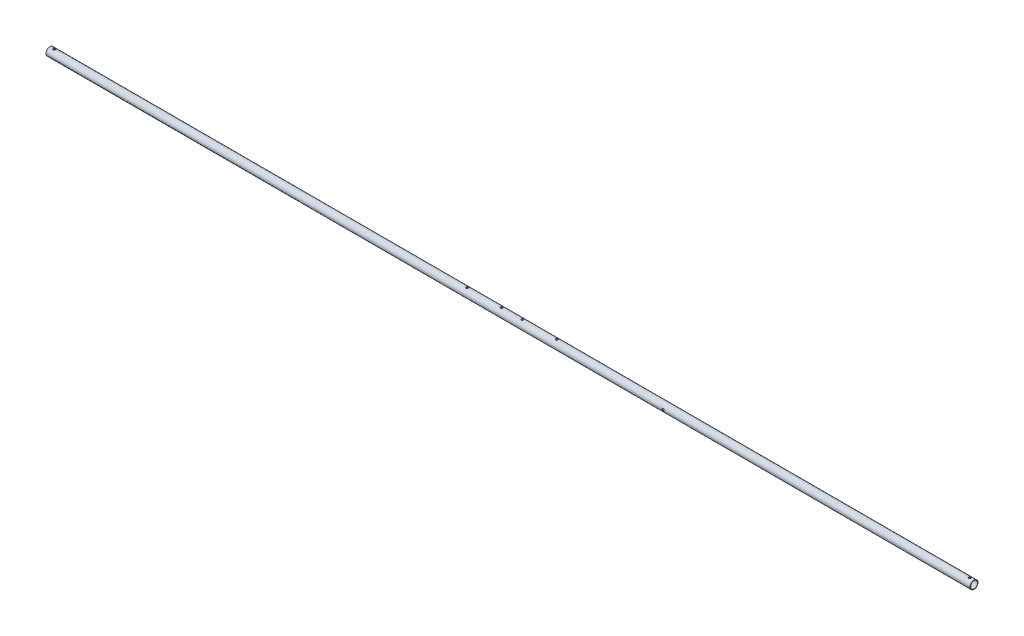
SolidWorks part; units mm, degrees
other "DetailItem1"
material "Galvanized Steel"
ref_plane "Front Plane" through (0, 0, 0) normal (0, 0, 1) x (1, 0, 0)
ref_plane "Top Plane" through (0, 0, 0) normal (0, 1, 0) x (1, 0, 0)
ref_plane "Right Plane" through (0, 0, 0) normal (1, 0, 0) x (0, 0, -1)
sketch "Sketch3" plane through (0, 0, 0) normal (1, 0, 0) x (0, 0, -1)
  circle A0 centre (0, 0) radius 10.4648
  circle A1 centre (0, 0) radius 11.7094
  dimension "D1" = 20.9296
  dimension "D2" = 23.4188
extrude "Boss-Extrude1" add sketch "Sketch3" along normal blind 2724.912
sketch "Sketch4" plane through (0, 0, 0) normal (0, 1, 0) x (1, 0, 0)
  line L0 (0, 11.7094) -> (0, -11.7094) construction
  circle A0 centre (1331.976, 0) radius 3.175
  circle A1 centre (1392.936, 0) radius 3.175
  circle A2 centre (1494.6376, 0) radius 3.175
  circle A3 centre (1230.2744, 0) radius 3.175
  point P0 (1362.456, 0)
  point P1 (1392.936, 0)
  point P3 (1331.976, 0)
  dimension "D4" = 6.35
  dimension "D5" = 6.35
  dimension "D6" = 132.1816
  dimension "D1" = 1362.456
  dimension "D2" = 30.48
  dimension "D3" = 30.48
  dimension "D7" = 132.1816
extrude "Cut-Extrude1" cut sketch "Sketch4" against normal through all and the other way through all
sketch "Sketch5" plane through (0, 0, 0) normal (0, 1, 0) x (1, 0, 0)
  line L0 (2724.912, -11.7094) -> (2724.912, 11.7094) construction
  circle A0 centre (12.7, 0) radius 3.175
  circle A1 centre (2712.212, 0) radius 3.175
  point P0 (12.7, 0)
  point P4 (2712.212, 0)
  dimension "D2" = 6.35
  dimension "D4" = 6.35
  dimension "D1" = 12.7
  dimension "D3" = 12.7
extrude "Cut-Extrude2" cut sketch "Sketch5" against normal through all and the other way through all
sketch "Sketch7" plane through (0, 0, 0) normal (0, 0, 1) x (1, 0, 0)
  circle A0 centre (1819.656, 0) radius 3.175
  spline S0 degree 2 poles (1335.151, 11.7094) (1331.976, 10.8485) (1328.801, 11.7094) knots 0 0 0 1 1 1 weights 0.008534 0.011709 0.014884 construction
  point P2 (1362.456, 0)
  dimension "D1" = 1362.456
  dimension "D2" = 457.2
extrude "Cut-Extrude3" cut sketch "Sketch7" against normal through all and the other way through all
equation "\"extrudelength\"=107.28"
equation "\"D1@Boss-Extrude1\"=\"extrudelength\""
equation "\"D1@Sketch7\"=\"extrudelength\"/2"
